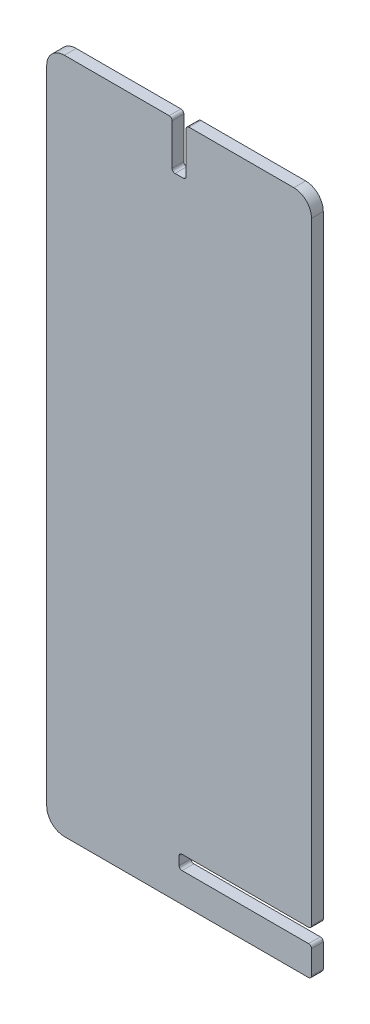
SolidWorks part; units mm, degrees
ref_plane "Alzado" through (0, 0, 0) normal (0, 0, 1) x (1, 0, 0)
ref_plane "Planta" through (0, 0, 0) normal (0, 1, 0) x (1, 0, 0)
ref_plane "Vista lateral" through (0, 0, 0) normal (1, 0, 0) x (0, 0, -1)
sketch "Croquis1" plane through (0, 0, 0) normal (0, 0, 1) x (1, 0, 0)
  line L1 (-22.5, 45) -> (22.5, 45)
  line L2 (-22.5, 45) -> (-22.5, -70)
  line L3 (-22.5, -70) -> (22.5, -70)
  line L4 (22.5, 45) -> (22.5, -70)
  dimension "D1" = 45
  dimension "D2" = 22.5
  dimension "D3" = 115
  dimension "D4" = 45
extrude "Saliente-Extruir1" add sketch "Croquis1" along normal blind 2 contours L2 L3 L4 L1
sketch "Croquis3" plane through (0, 0, 2) normal (0, 0, 1) x (1, 0, 0)
  line L0 (22.5, 45) -> (22.5, -70) construction
  line L1 (22.5, -62.6) -> (0, -62.6)
  line L2 (22.5, -62.6) -> (22.5, -65)
  line L3 (22.5, -65) -> (0, -65)
  line L4 (0, -62.6) -> (0, -65)
  line L5 (-22.5, -70) -> (22.5, -70) construction
  dimension "D1" = 2.4
  dimension "D2" = 5
  dimension "D3" = 22.5
extrude "Cortar-Extruir2" cut sketch "Croquis3" against normal up to surface (2 mm away) up to face at (0, -12.5, 0)
fillet "Redondeo1" radius 3 3 edges at (-22.5, -70, 1) (22.5, 45, 1) (-22.5, 45, 1)
sketch "Croquis4" plane through (0, 0, 2) normal (0, 0, 1) x (1, 0, 0)
  line L5 (0, 0) -> (0, 53.685) construction
  line L6 (-19.5, 45) -> (19.5, 45) construction
  line L7 (-1.2, 45) -> (1.2, 45)
  line L8 (-1.2, 45) -> (-1.2, 37)
  line L9 (-1.2, 37) -> (1.2, 37)
  line L10 (1.2, 45) -> (1.2, 37)
  dimension "D1" = 1.2
  dimension "D2" = 1.2
  dimension "D3" = 8
extrude "Cortar-Extruir3" cut sketch "Croquis4" against normal up to surface (2 mm away) up to face at (2.2617, -26.1435, 0)
fillet "Redondeo2" radius 0.5 9 edges at (0, -62.6, 1) (0, -65, 1) (22.5, -70, 1) (22.5, -65, 1) (22.5, -62.6, 1) (-1.2, 37, 1) (1.2, 37, 1) (-1.2, 45, 1) (1.2, 45, 1)
